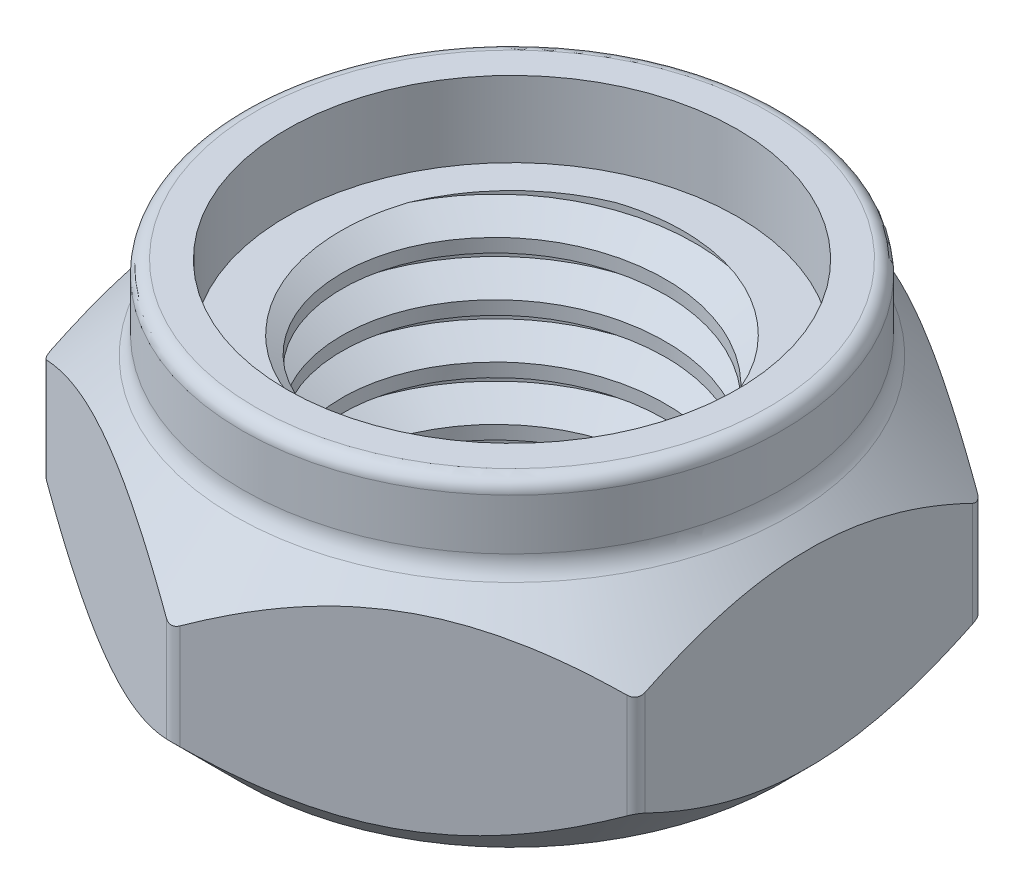
SolidWorks part; units mm, degrees
ref_plane "Front Plane" through (0, 0, 0) normal (0, 0, 1) x (1, 0, 0)
ref_plane "Top Plane" through (0, 0, 0) normal (0, 1, 0) x (1, 0, 0)
ref_plane "Right Plane" through (0, 0, 0) normal (1, 0, 0) x (0, 0, -1)
sketch "Sketch1" plane through (0, 0, 0) normal (0, 1, 0) x (1, 0, 0)
  line L1 (0, 6.3509) -> (-5.5, 3.1754)
  line L2 (-5.5, 3.1754) -> (-5.5, -3.1754)
  line L3 (-5.5, -3.1754) -> (0, -6.3509)
  line L4 (0, -6.3509) -> (5.5, -3.1754)
  line L5 (5.5, -3.1754) -> (5.5, 3.1754)
  line L6 (5.5, 3.1754) -> (0, 6.3509)
  circle A0 centre (0, 0) radius 5.5 construction
  dimension "D1" = 11
extrude "Boss-Extrude1" add sketch "Sketch1" along normal blind 6
sketch "Sketch2" plane through (0, 6, 0) normal (0, 1, 0) x (1, 0, 0)
  circle A0 centre (0, 0) radius 3
  dimension "D1" = 6
extrude "Cut-Extrude1" cut sketch "Sketch2" against normal blind 6
thread "Thread1" pitch 1 method cut profile "Thread Profile1" start angle 0, offset 0, length 0, pitch 1, diameter 6
ref_plane "Plane1" through (-3, 6, 0) normal (0, 0, 1) x (-1, 0, 0)
sketch "Thread Profile1" plane through (-3, 6, 0) normal (0, 0, 1) x (-1, 0, 0)
  line L0 (0, 0) -> (0, 1) construction
  line L1 (0, 0) -> (0.5413, 0.3125)
  line L2 (0.5413, 0.3125) -> (0.5413, 0.4375)
  line L3 (0.5413, 0.4375) -> (0, 0.75)
  line L4 (0.5413, 0.375) -> (0, 0.375) construction
  line L11 (0, 0) -> (0, 0.75)
  point P2 (0, 0)
  dimension "Pitch" = 1
  dimension "Profile_Angle" = 60
  dimension "Profile_Land" = 0.125
  dimension "Profile_Height" = 0.5413
sketch "Sketch8" plane through (0, 6, 0) normal (0, 1, 0) x (1, 0, 0)
  circle A0 centre (0, 0) radius 7.8115
extrude "Cut-Extrude3" cut sketch "Sketch8" against normal blind 1.5 contours A0
sketch "Sketch9" plane through (0, 0, 0) normal (0, 0, 1) x (1, 0, 0)
  line L0 (0, -1.8255) -> (0, 6.4438) construction
  line L1 (-6.5, 3) -> (-6.5, 5.5)
  line L2 (-6.5, 5.5) -> (-4, 5.5)
  line L3 (-4, 5.5) -> (-6.5, 3)
  line L4 (-6.5, 1.5) -> (-6.5, -1)
  line L5 (-6.5, -1) -> (-4, -1)
  line L6 (-4, -1) -> (-6.5, 1.5)
  line L7 (-5.5, 4.5) -> (-5.5, 0) construction
  line L8 (-5.5, 4.5) -> (0, 4.5) construction
  line L9 (-5.5, 0) -> (0, 0) construction
  dimension "D1" = 1
  dimension "D2" = 1
  dimension "D3" = 1
  dimension "D4" = 1
  dimension "D5" = 2.5
  dimension "D6" = 2.5
  dimension "D7" = 2.5
  dimension "D8" = 2.5
revolve "Cut-Revolve3" cut sketch "Sketch9" angle 360 about L0 reverse direction yes
sketch "Sketch10" plane through (0, 4.5, 0) normal (0, 1, 0) x (1, 0, 0)
  circle A0 centre (0, 0) radius 5
  circle A1 centre (0, 0) radius 4.175
  dimension "D1" = 10
  dimension "D2" = 8.35
extrude "Boss-Extrude2" add sketch "Sketch10" along normal blind 1.4
fillet "Fillet1" radius 0.5 1 edges at (0, 4.5, 5)
fillet "Fillet2" radius 0.25 7 edges at (0, 2.25, -6.3509) (5.5, 2.25, -3.1754) (5.5, 2.25, 3.1754) (0, 2.25, 6.3509) (-5.5, 2.25, 3.1754) (-5.5, 2.25, -3.1754) (0, 5.9, 5)
